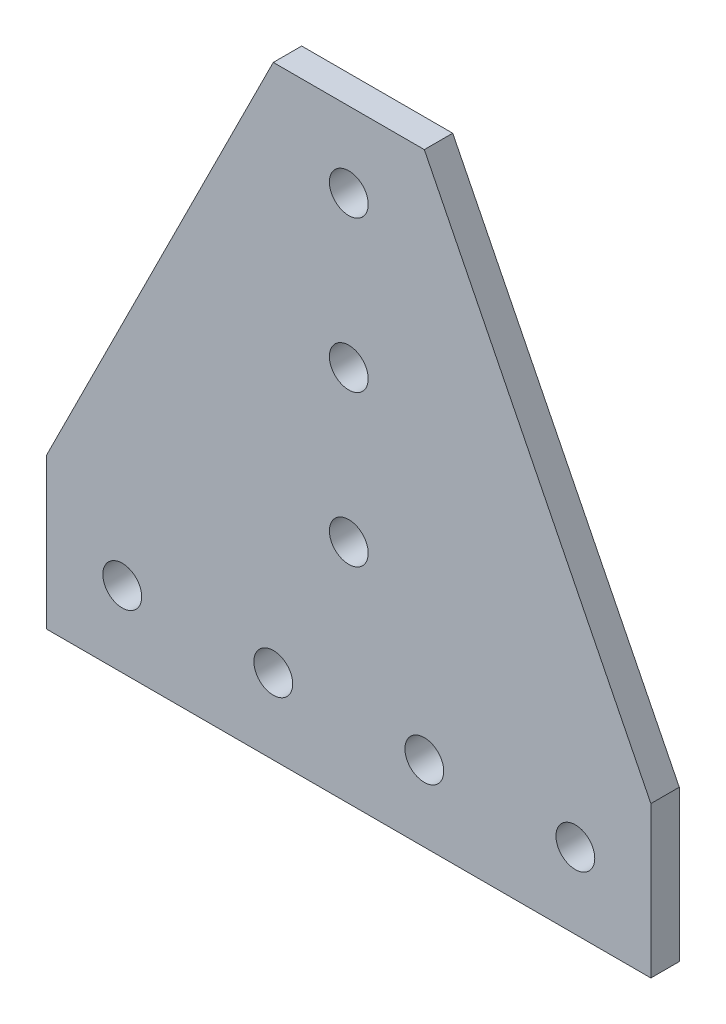
SolidWorks part; units mm, degrees
ref_plane "Front Plane" through (0, 0, 0) normal (0, 0, 1) x (1, 0, 0)
ref_plane "Top Plane" through (0, 0, 0) normal (0, 1, 0) x (1, 0, 0)
ref_plane "Right Plane" through (0, 0, 0) normal (1, 0, 0) x (0, 0, -1)
sketch "Sketch1" plane through (0, 0, 0) normal (0, 0, 1) x (1, 0, 0)
  line L0 (50.8, -50.8) -> (-50.8, -50.8) construction
  line L1 (0, 50.8) -> (0, -50.8) construction
  line L2 (50.8, -50.8) -> (50.8, -25.4) construction
  line L3 (-41.3639, -38.1) -> (-34.8361, -38.1) construction
  point P0 (50.8, -38.1)
  point P3 (0, -50.8)
  point P7 (0, 0)
  point P9 (-12.7, -38.1)
  point P12 (-38.1, -38.1)
  point P18 (50.8, 50.8)
sketch "Sketch2" plane through (0, 0, 0) normal (1, 0, 0) x (0, 0, -1)
  line L0 (2.3876, 0) -> (-2.3876, 0) construction
  point P4 (0, 0)
  dimension "Thickness" = 4.7752
sketch "Sketch3" plane through (0, 0, 0) normal (0, 0, 1) x (1, 0, 0)
  line L0 (50.8, -50.8) -> (-50.8, -50.8)
  line L1 (50.8, -50.8) -> (50.8, -25.4)
  line L2 (50.8, -25.4) -> (12.7, 50.8)
  line L3 (12.7, 50.8) -> (-12.7, 50.8)
  line L4 (50.8, -50.8) -> (-50.8, -50.8) construction
  line L5 (0, -50.8) -> (0, 50.8) construction
  line L6 (-50.8, -25.4) -> (-12.7, 50.8)
  line L7 (-50.8, -50.8) -> (-50.8, -25.4)
extrude "Boss-Extrude1" add sketch "Sketch3" against normal up to vertex (2.3876 mm away) and the other way up to vertex (2.3876 mm away) contours L3 L6 L7 L0 L1 L2 up to point (0, 0, -2.3876) other way up to point (0, 0, 2.3876)
sketch "Sketch4" plane through (0, 0, 2.3876) normal (0, 0, 1) x (1, 0, 0)
  line L0 (0, -50.8) -> (0, 50.8) construction
  line L1 (50.8, -50.8) -> (-50.8, -50.8) construction
  line L2 (12.7, 50.8) -> (-12.7, 50.8) construction
  line L3 (-41.3639, -38.1) -> (-34.8361, -38.1) construction
  line L4 (-38.1, -38.1) -> (-12.7, -38.1) construction
  line L5 (0, 38.1) -> (0, 12.7) construction
  circle A0 centre (-38.1, -38.1) radius 3.2639
  circle A5 centre (-12.7, -38.1) radius 3.2639
  circle A6 centre (12.7, -38.1) radius 3.2639
  circle A9 centre (0, 38.1) radius 3.2639
  circle A10 centre (0, 12.7) radius 3.2639
  circle A11 centre (38.1, -38.1) radius 3.2639
  circle A12 centre (0, -12.7) radius 3.2639
  dimension "D2" = 25.4
  dimension "D3" = 12.7
  dimension "D5" = 25.4
  dimension "D1" = 4
  dimension "D4" = 3
extrude "Cut-Extrude1" cut sketch "Sketch4" against normal through all
ref_axis "Axis1" through (0, 50.8, 2.3876) along (0, 0, -1)
equation "\"D1@Sketch4\"=\"#Holes@Sketch1\""
equation "\"D2@Sketch4\"=\"Hole Spacing@Sketch1\""
equation "\"D3@Sketch4\"=\"Hole to Edge@Sketch1\""
equation "\"D5@Sketch4\"=\"Hole Spacing@Sketch1\""
equation "\"D4@Sketch4\"=\"#Holes@Sketch1\"-1"
